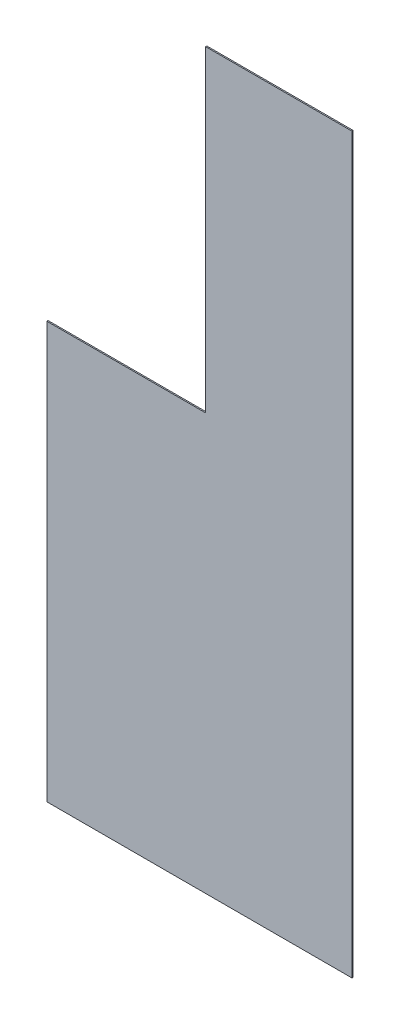
SolidWorks part; units mm, degrees
material "Hardox"
ref_plane "Ön Düzlem" through (0, 0, 0) normal (0, 0, 1) x (1, 0, 0)
ref_plane "Üst Düzlem" through (0, 0, 0) normal (0, 1, 0) x (1, 0, 0)
ref_plane "Sağ Düzlem" through (0, 0, 0) normal (1, 0, 0) x (0, 0, -1)
sketch "Çizim1" plane through (0, 0, 0) normal (0, 0, 1) x (1, 0, 0)
  line L0 (0, 0) -> (0, 3417)
  line L1 (0, 3417) -> (1305, 3417)
  line L2 (1305, 3417) -> (1305, 6021)
  line L3 (1305, 6021) -> (2506, 6021)
  line L4 (2506, 6021) -> (2506, 0)
  line L5 (2506, 0) -> (0, 0)
  dimension "D1" = 3417
  dimension "D2" = 1305
  dimension "D3" = 2604
  dimension "D4" = 1201
  dimension "D5" = 2506
  dimension "D6" = 6021
base flange "Taban-Flanş1" sketch "Çizim1" thickness 10 reverse thickness direction no parameters "D1"=4
sketch "Büküm-Çizgileri1" [suppressed] plane through (0, 0, 0) normal (0, 1, 0) x (1, 0, 0)
sketch "Sınırlandırma-Kutusu1" [suppressed] plane through (0, 0, 0) normal (0, 1, 0) x (1, 0, 0)
sheet metal parameters "Sac-Levha1" thickness 10 parameters "D1"=4
flat pattern "Düz-Çoğaltma1" [suppressed]
sketch "Büküm-Çizgileri2" plane through (0, 0, 0) normal (0, 1, 0) x (1, 0, 0)
sketch3d "Sınırlandırma-Kutusu2" [suppressed]
  line L0 (2506, 6021, 0) -> (2506, 0, 0) construction
  line L1 (0, 6021, 0) -> (0, 0, 0) construction
  line L2 (2506, 6021, 0) -> (0, 6021, 0) construction
  line L3 (2506, 0, 0) -> (0, 0, 0) construction
